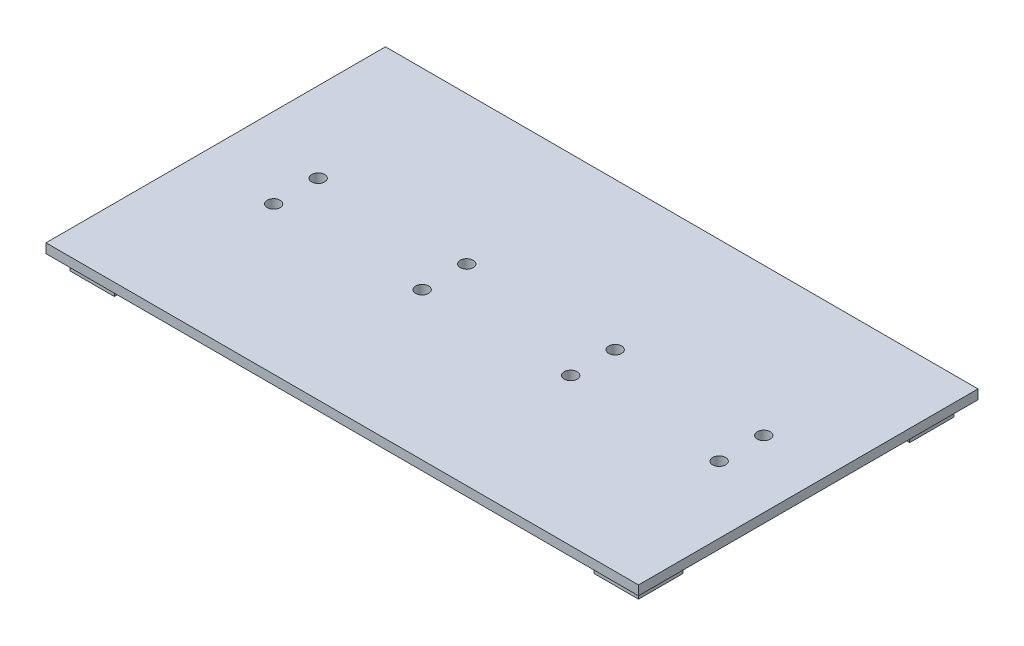
SolidWorks part; units mm, degrees
ref_plane "Front Plane" through (0, 0, 0) normal (0, 0, 1) x (1, 0, 0)
ref_plane "Top Plane" through (0, 0, 0) normal (0, 1, 0) x (1, 0, 0)
ref_plane "Right Plane" through (0, 0, 0) normal (1, 0, 0) x (0, 0, -1)
sketch "Sketch1" plane through (0, 0, 0) normal (0, 1, 0) x (1, 0, 0)
  line L1 (0, 0) -> (399, 0)
  line L2 (0, 0) -> (0, -228.6)
  line L3 (0, -228.6) -> (399, -228.6)
  line L4 (399, 0) -> (399, -228.6)
  dimension "D1" = 399
  dimension "D2" = 228.6
extrude "Base" add sketch "Sketch1" against normal blind 6.35
sketch "Sketch9" plane through (0, 0, 0) normal (0, 1, 0) x (1, 0, 0)
  line L0 (0, -114.3) -> (399, -114.3) construction
  line L1 (0, 0) -> (0, -228.6) construction
  line L2 (399, -228.6) -> (399, 0) construction
  point P7 (0, 0)
  point P9 (254, -129.3)
  point P10 (254, -99.3)
  point P12 (354, -129.3)
  point P13 (354, -99.3)
  point P15 (154, -129.3)
  point P16 (154, -99.3)
  point P19 (54, -129.3)
  point P20 (54, -99.3)
  point P21 (304, -129.3)
  point P22 (304, -99.3)
  point P23 (204, -129.3)
  point P24 (204, -99.3)
  point P25 (104, -129.3)
  point P26 (104, -99.3)
  dimension "D2" = 45
  dimension "D3" = 15
  dimension "D4" = 100
  dimension "D1" = 7
hole_wizard "Hole for 1/4 Blind Fasteners (B,BS)1" positions "Sketch10" profile "Sketch11" hole size "1/4-20" standard "PEM® Inch" end condition through all
sketch "Sketch10" plane through (0, 0, 0) normal (0, 1, 0) x (1, 0, 0)
  point P0 (354, -129.3)
  point P6 (254, -129.3)
  point P12 (154, -129.3)
  point P18 (54, -129.3)
  point P21 (54, -99.3)
  point P27 (154, -99.3)
  point P33 (254, -99.3)
  point P39 (354, -99.3)
  point P42 (0, 0)
sketch "Sketch11" plane through (354, 0, 129.3) normal (1, 0, 0) x (0, 0, 1)
  line L0 (0, 0) -> (0, 6.35)
  line L1 (0, 6.35) -> (4.3688, 6.35)
  line L2 (4.3688, 6.35) -> (4.3688, 0)
  line L5 (4.3688, 0) -> (0, 0)
  line L11 (0, -6.35) -> (0, 107.95) construction
  dimension "Thru Hole Dia." = 8.7376
  dimension "Thru Hole Depth" = 6.35
sketch "Sketch12" plane through (0, -6.35, 0) normal (0, -1, 0) x (1, 0, 0)
  line L0 (0, 228.6) -> (399, 228.6) construction
  line L1 (8, 220.6) -> (38, 220.6)
  line L2 (8, 220.6) -> (8, 190.6)
  line L3 (8, 190.6) -> (38, 190.6)
  line L4 (38, 220.6) -> (38, 190.6)
  line L5 (0, 0) -> (0, 228.6) construction
  line L6 (199.5, 228.6) -> (199.5, 0) construction
  line L7 (399, 0) -> (0, 0) construction
  line L8 (0, 114.3) -> (399, 114.3) construction
  line L9 (399, 228.6) -> (399, 0) construction
  line L10 (8, 38) -> (38, 38)
  line L11 (38, 8) -> (38, 38)
  line L12 (8, 8) -> (38, 8)
  line L13 (8, 8) -> (8, 38)
  line L14 (391, 8) -> (391, 38)
  line L15 (391, 8) -> (361, 8)
  line L16 (361, 8) -> (361, 38)
  line L17 (391, 38) -> (361, 38)
  line L18 (391, 190.6) -> (361, 190.6)
  line L19 (361, 220.6) -> (361, 190.6)
  line L20 (391, 220.6) -> (361, 220.6)
  line L21 (391, 220.6) -> (391, 190.6)
  dimension "D1" = 30
  dimension "D2" = 30
extrude "Boss-Extrude1" add sketch "Sketch12" along normal blind 10
